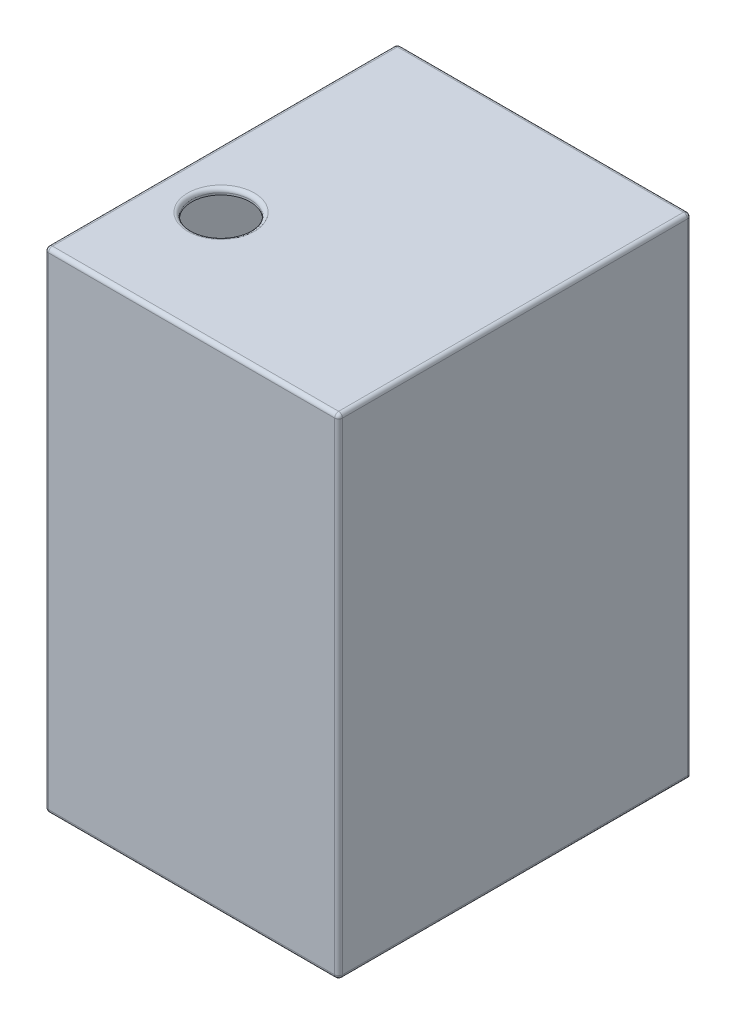
SolidWorks part; units mm, degrees
ref_plane "Front Plane" through (0, 0, 0) normal (0, 0, 1) x (1, 0, 0)
ref_plane "Top Plane" through (0, 0, 0) normal (0, 1, 0) x (1, 0, 0)
ref_plane "Right Plane" through (0, 0, 0) normal (1, 0, 0) x (0, 0, -1)
sketch "Sketch1" plane through (0, 0, 0) normal (0, 0, 1) x (1, 0, 0)
  line L1 (0, 0) -> (150, 0)
  line L2 (0, 0) -> (0, -250)
  line L3 (0, -250) -> (150, -250)
  line L4 (150, 0) -> (150, -250)
  dimension "D1" = 150
  dimension "D2" = 250
extrude "Boss-Extrude1" add sketch "Sketch1" along normal blind 180
shell "Shell1" thickness 3 removed face at (75, 0, 90)
sketch "Sketch2" plane through (0, 0, 0) normal (0, 0, 1) x (1, 0, 0)
  line L0 (0, 0) -> (150, 0)
  line L1 (150, 0) -> (150, -3)
  line L2 (150, -250) -> (150, 0) construction
  line L3 (150, -3) -> (0, -3)
  line L4 (0, 0) -> (0, -250) construction
  line L5 (0, -3) -> (0, 0)
  dimension "D1" = 3
extrude "Boss-Extrude2" add sketch "Sketch2" along normal blind 180
sketch "Sketch3" plane through (0, 0, 0) normal (0, 1, 0) x (1, 0, 0)
  line L0 (0, -180) -> (0, 0) construction
  line L1 (150, -180) -> (0, -180) construction
  circle A0 centre (30, -120) radius 15
  dimension "D1" = 30
  dimension "D2" = 30
  dimension "D3" = 60
extrude "Cut-Extrude1" cut sketch "Sketch3" against normal blind 10
sketch "Sketch4" plane through (150, 0, 0) normal (1, 0, 0) x (0, 0, -1)
  line L0 (-180, -250) -> (0, -250) construction
  line L3 (-180, -250) -> (-180, 0) construction
  circle A0 centre (-100, -235) radius 13
  circle A1 centre (-100, -235) radius 15
  dimension "D1" = 26
  dimension "D4" = 30
  dimension "D2" = 15
  dimension "D3" = 80
fillet "Fillet1" radius 2 12 edges at (0, 0, 90) (150, 0, 90) (0, -250, 90) (150, -250, 90) (0, -125, 0) (150, -125, 0) (75, 0, 0) (75, 0, 180) (150, -125, 180) (75, -250, 180) (0, -125, 180) (30, 0, 135)
sketch "Sketch6" plane through (150, 0, 0) normal (1, 0, 0) x (0, 0, -1)
  line L0 (-178, -250) -> (-2, -250) construction
  line L1 (-178, -2) -> (-178, -248) construction
  circle A0 centre (-98, -235) radius 15
  circle A1 centre (-98, -235) radius 13
  dimension "D1" = 26
  dimension "D2" = 30
  dimension "D3" = 15
  dimension "D4" = 80
sketch "Sketch9" plane through (0, 0, 0) normal (0, 0, -1) x (-1, 0, 0)
  line L0 (-2, -250) -> (-148, -250) construction
  line L1 (-150, -248) -> (-150, -2) construction
  circle A0 centre (-70, -235) radius 13
  circle A1 centre (-70, -235) radius 15
  dimension "D1" = 30
  dimension "D2" = 26
  dimension "D3" = 15
  dimension "D4" = 80
extrude "Cut-Extrude2" cut sketch "Sketch9" against normal blind 15 contours A0 region at (70, -235, 0)
extrude "Boss-Extrude3" add sketch "Sketch9<3>" along normal blind 40
sketch "Sketch9<3>" plane through (0, 0, 0) normal (0, 0, -1) x (-1, 0, 0) same geometry as "Sketch9"
sketch "Sketch5" plane through (150, 0, 0) normal (1, 0, 0) x (0, 0, -1)
  line L0 (-178, -248) -> (-2, -248) construction
  line L1 (-178, -2) -> (-178, -248) construction
  circle A0 centre (-98, -233) radius 15
  dimension "D1" = 30
  dimension "D2" = 15
  dimension "D3" = 80
